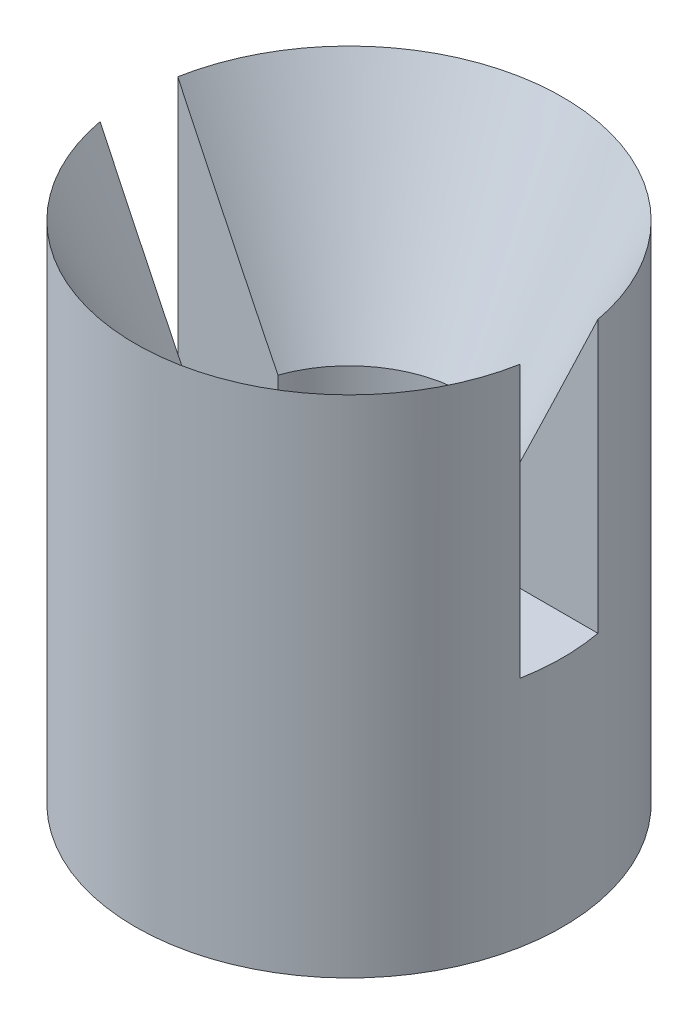
SolidWorks part; units mm, degrees
material "Cast Alloy Steel"
ref_plane "Front Plane" through (0, 0, 0) normal (0, 0, 1) x (1, 0, 0)
ref_plane "Top Plane" through (0, 0, 0) normal (0, 1, 0) x (1, 0, 0)
ref_plane "Right Plane" through (0, 0, 0) normal (1, 0, 0) x (0, 0, -1)
sketch "Sketch1" plane through (0, 0, 0) normal (0, 1, 0) x (1, 0, 0)
  circle A0 centre (0, 0) radius 5.5
  dimension "D1" = 11
extrude "Boss-Extrude1" add sketch "Sketch1" along normal blind 13
sketch "Sketch2" plane through (0, 13, 0) normal (0, 1, 0) x (1, 0, 0)
  circle A0 centre (0, 0) radius 3
extrude "Cut-Extrude1" cut sketch "Sketch2" against normal blind 7
chamfer "Chamfer1" distance 2.5 angle 65 1 edges at (0, 13, 3) first distance on face at (0, 13, 3)
ref_plane "Plane1" through (0, 13, 0) normal (0, -1, 0) x (-1, 0, 0)
sketch "Sketch3" plane through (0, 13, 0) normal (0, -1, 0) x (-1, 0, 0)
  line L1 (5.8087, 1) -> (-5.8087, 1)
  line L2 (5.8087, 1) -> (5.8087, -1)
  line L3 (5.8087, -1) -> (-5.8087, -1)
  line L4 (-5.8087, 1) -> (-5.8087, -1)
  line L5 (5.8087, 1) -> (-5.8087, -1) construction
  line L6 (5.8087, -1) -> (-5.8087, 1) construction
  point P0 (0, 0)
  dimension "D1" = 2
extrude "Cut-Extrude2" cut sketch "Sketch3" along normal blind 7
sketch "Sketch4" plane through (0, 0, 0) normal (0, -1, 0) x (1, 0, 0)
  circle A0 centre (0, 0) radius 2.5
  dimension "D1" = 5
extrude "Cut-Extrude3" cut sketch "Sketch4" against normal blind 7
ref_plane "Plane2" through (0, 0, -5.5) normal (0, 0, -1) x (-1, 0, 0)
sketch "Sketch5" plane through (0, 0, -5.5) normal (0, 0, -1) x (-1, 0, 0)
  line L0 (-5.5, 0) -> (5.5, 0) construction
  circle A0 centre (0, 4) radius 1
  dimension "D1" = 2
  dimension "D2" = 4
extrude "Cut-Extrude5" cut sketch "Sketch5" against normal blind 4
cosmetic thread "Cosmetic Thread2" parameters "D2"=2.5
equation "\"1§\"=5"
